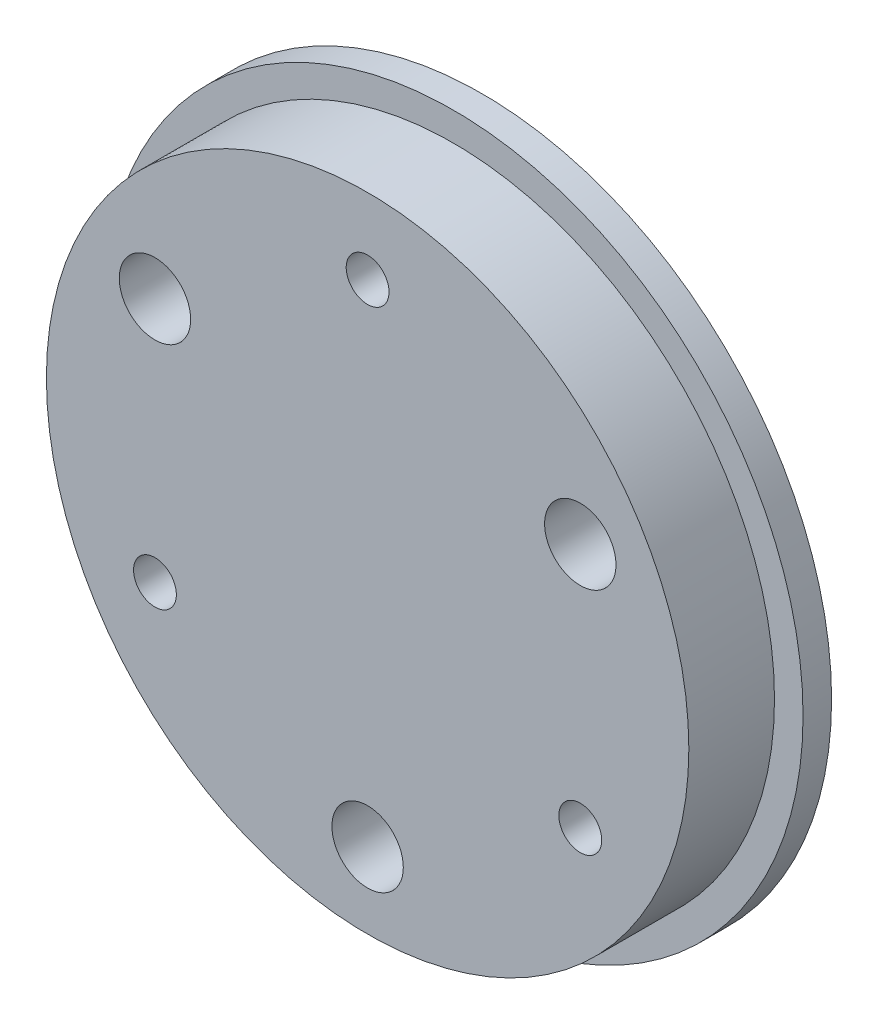
SolidWorks part; units mm, degrees
ref_plane "Front Plane" through (0, 0, 0) normal (0, 0, 1) x (1, 0, 0)
ref_plane "Top Plane" through (0, 0, 0) normal (0, 1, 0) x (1, 0, 0)
ref_plane "Right Plane" through (0, 0, 0) normal (1, 0, 0) x (0, 0, -1)
sketch "Sketch1" plane through (0, 0, 0) normal (0, 0, 1) x (1, 0, 0)
  circle A0 centre (0, 0) radius 22.5
  circle A1 centre (0, 0) radius 24.5
  circle A2 centre (0, 0) radius 17.2 construction
  circle A3 centre (0, 17.2) radius 1.5
  circle A4 centre (14.8956, -8.6) radius 1.5
  circle A5 centre (-14.8956, -8.6) radius 1.5
  circle A6 centre (0, -17.2) radius 2.5
  circle A7 centre (-14.8956, 8.6) radius 2.5
  circle A8 centre (14.8956, 8.6) radius 2.5
  point P7 (0, 0)
  point P13 (0, 0)
  point P20 (0, 0)
  dimension "D1" = 45
  dimension "D2" = 49
  dimension "D3" = 34.4
  dimension "D4" = 3
  dimension "D6" = 5
  dimension "D5" = 3
  dimension "D7" = 3
extrude "Boss-Extrude1" add sketch "Sketch1" along normal blind 2 contours A1 A0 region at (-23.807, 0, 0)
extrude "Boss-Extrude2" add sketch "Sketch1<3>" along normal blind 8 contours A0 A8 A7 A6 A5 A4 A3 region at (0, 0, 0)
sketch "Sketch1<3>" plane through (0, 0, 0) normal (0, 0, 1) x (1, 0, 0) same geometry as "Sketch1"
